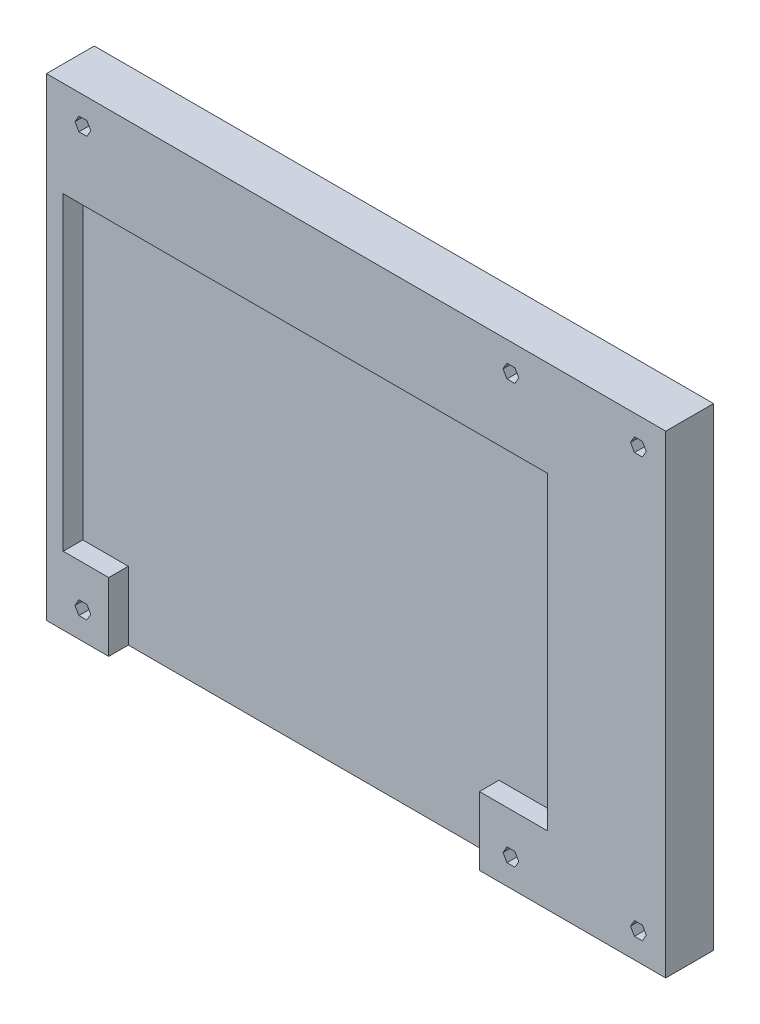
SolidWorks part; units mm, degrees
ref_plane "前视基准面" through (0, 0, 0) normal (0, 0, 1) x (1, 0, 0)
ref_plane "上视基准面" through (0, 0, 0) normal (0, 1, 0) x (1, 0, 0)
ref_plane "右视基准面" through (0, 0, 0) normal (1, 0, 0) x (0, 0, -1)
sketch "草图1" plane through (0, 0, 0) normal (0, 0, 1) x (1, 0, 0)
  line L0 (8, 104) -> (8, 0) construction
  line L1 (0, 0) -> (136, 0)
  line L2 (0, 0) -> (0, 104)
  line L3 (0, 104) -> (136, 104)
  line L4 (136, 0) -> (136, 104)
  line L5 (0, 6) -> (136, 6) construction
  line L6 (0, 98) -> (136, 98) construction
  line L7 (130, 104) -> (130, 0) construction
  line L9 (7.38, 80.5) -> (106.38, 80.5) construction
  line L10 (7.38, 80.5) -> (7.38, 23.5) construction
  line L11 (7.38, 23.5) -> (106.38, 23.5) construction
  line L12 (106.38, 80.5) -> (106.38, 23.5) construction
  line L13 (7.38, 80.5) -> (106.38, 23.5) construction
  line L14 (7.38, 23.5) -> (106.38, 80.5) construction
  line L19 (3.68, 83) -> (110.08, 83)
  line L20 (3.68, 83) -> (3.68, 15)
  line L21 (3.68, 15) -> (110.08, 15)
  line L22 (110.08, 83) -> (110.08, 15)
  line L23 (3.68, 83) -> (110.08, 15) construction
  line L24 (3.68, 15) -> (110.08, 83) construction
  line L25 (13.68, 15) -> (95.08, 15)
  line L26 (13.68, 15) -> (13.68, 0)
  line L27 (13.68, 0) -> (95.08, 0)
  line L28 (95.08, 15) -> (95.08, 0)
  line L29 (13.68, 15) -> (95.08, 0) construction
  line L30 (13.68, 0) -> (95.08, 15) construction
  line L31 (9.7321, 6) -> (8.866, 7.5)
  line L32 (8.866, 7.5) -> (7.134, 7.5)
  line L33 (7.134, 7.5) -> (6.2679, 6)
  line L34 (6.2679, 6) -> (7.134, 4.5)
  line L35 (7.134, 4.5) -> (8.866, 4.5)
  line L36 (8.866, 4.5) -> (9.7321, 6)
  line L37 (128.2679, 6) -> (129.134, 4.5)
  line L38 (129.134, 4.5) -> (130.866, 4.5)
  line L39 (130.866, 4.5) -> (131.7321, 6)
  line L40 (131.7321, 6) -> (130.866, 7.5)
  line L41 (130.866, 7.5) -> (129.134, 7.5)
  line L42 (129.134, 7.5) -> (128.2679, 6)
  line L43 (131.7321, 98) -> (130.866, 99.5)
  line L44 (130.866, 99.5) -> (129.134, 99.5)
  line L45 (129.134, 99.5) -> (128.2679, 98)
  line L46 (128.2679, 98) -> (129.134, 96.5)
  line L47 (129.134, 96.5) -> (130.866, 96.5)
  line L48 (130.866, 96.5) -> (131.7321, 98)
  line L49 (9.7321, 98) -> (8.866, 99.5)
  line L50 (8.866, 99.5) -> (7.134, 99.5)
  line L51 (7.134, 99.5) -> (6.2679, 98)
  line L52 (6.2679, 98) -> (7.134, 96.5)
  line L53 (7.134, 96.5) -> (8.866, 96.5)
  line L54 (8.866, 96.5) -> (9.7321, 98)
  line L55 (101.134, 99.5) -> (100.2679, 98)
  line L56 (100.2679, 98) -> (101.134, 96.5)
  line L57 (101.134, 96.5) -> (102.866, 96.5)
  line L58 (102.866, 96.5) -> (103.7321, 98)
  line L59 (103.7321, 98) -> (102.866, 99.5)
  line L60 (102.866, 99.5) -> (101.134, 99.5)
  line L65 (103.7321, 6) -> (102.866, 7.5)
  line L66 (102.866, 7.5) -> (101.134, 7.5)
  line L67 (101.134, 7.5) -> (100.2679, 6)
  line L68 (100.2679, 6) -> (101.134, 4.5)
  line L69 (101.134, 4.5) -> (102.866, 4.5)
  line L70 (102.866, 4.5) -> (103.7321, 6)
  circle A4 centre (8, 6) radius 1.5 construction
  circle A5 centre (130, 6) radius 1.5 construction
  circle A6 centre (130, 98) radius 1.5 construction
  circle A7 centre (8, 98) radius 1.5 construction
  circle A8 centre (102, 98) radius 1.5 construction
  circle A9 centre (102, 6) radius 1.5 construction
  point P17 (56.88, 52)
  point P18 (56.88, 52)
  point P23 (56.88, 49)
  point P28 (54.38, 7.5)
  point P29 (8, 6)
  point P30 (130, 6)
  point P31 (130, 98)
  point P32 (8, 98)
  point P36 (118.1646, 6)
  point P74 (0, 0)
  dimension "D18" = 3
  dimension "D19" = 3
  dimension "D20" = 3
  dimension "D21" = 3
  dimension "D22" = 3
  dimension "D24" = 3
  dimension "D2" = 6
  dimension "D3" = 122
  dimension "D4" = 92
  dimension "D5" = 99
  dimension "D6" = 57
  dimension "D7" = 0.62
  dimension "D8" = 17.5
  dimension "D9" = 8.5
  dimension "D10" = 2.5
  dimension "D11" = 3.7
  dimension "D12" = 3.7
  dimension "D13" = 8
  dimension "D14" = 6
  dimension "D15" = 6
  dimension "D16" = 10
  dimension "D17" = 15
  dimension "D23" = 94
  dimension "D25" = 94
extrude "凸台-拉伸1" add sketch "草图1" against normal blind 10.5 contours L1 L4 L3 L2
extrude "屏幕坑" cut sketch "草图1<3>" against normal blind 4.3 contours L22 L19 L20 L21 | L28 L21 L26 L1 region at (54.38, 7.5, 0) region at (56.88, 49, 0)
sketch "草图1<3>" plane through (0, 0, 0) normal (0, 0, 1) x (1, 0, 0) same geometry as "草图1"
extrude "六角坑" cut sketch "草图1<5>" against normal up to next contours L53 L54 L49 L50 L51 L52 | L47 L48 L43 L44 L45 L46 | L41 L42 L37 L38 L39 L40 | L35 L36 L31 L32 L33 L34 | L69 L70 L65 L66 L67 L68 | L59 L60 L55 L56 L57 L58 region at (8, 6, 0) region at (130, 6, 0) region at (130, 98, 0) region at (8, 98, 0) region at (102, 98, 0) region at (102, 6, 0)
sketch "草图1<5>" plane through (0, 0, 0) normal (0, 0, 1) x (1, 0, 0) same geometry as "草图1"
sketch "草图4" plane through (0, 0, -10.5) normal (0, 0, -1) x (-1, 0, 0)
  line L0 (-8.866, 7.5) -> (-7.134, 7.5) construction
  line L1 (-5.2679, 9.5) -> (-20.2679, 9.5)
  line L2 (-5.2679, 9.5) -> (-5.2679, 44.5)
  line L3 (-5.2679, 44.5) -> (-20.2679, 44.5)
  line L4 (-20.2679, 9.5) -> (-20.2679, 44.5)
  line L5 (-5.2679, 9.5) -> (-20.2679, 44.5) construction
  line L6 (-5.2679, 44.5) -> (-20.2679, 9.5) construction
  line L8 (0, 0) -> (0, 104) construction
  line L9 (-5.2679, 44.5) -> (0, 44.5)
  line L10 (-5.2679, 44.5) -> (-5.2679, 9.5)
  line L11 (-5.2679, 9.5) -> (0, 9.5)
  line L12 (0, 44.5) -> (0, 9.5)
  line L13 (-5.2679, 44.5) -> (0, 9.5) construction
  line L14 (-5.2679, 9.5) -> (0, 44.5) construction
  point P4 (-12.7679, 27)
  point P7 (-8, 7.5)
  point P12 (-2.634, 27)
  line M41 (0, 0) -> (0, 104)
  dimension "D1" = 2
  dimension "D2" = 35
  dimension "D3" = 15
  dimension "D4" = 1
extrude "PCB插件坑" cut sketch "草图4" against normal blind 3 contours L2 L11 L9 M41 | L2 L1 L4 L3 region at (2.634, 27, -10.5)
